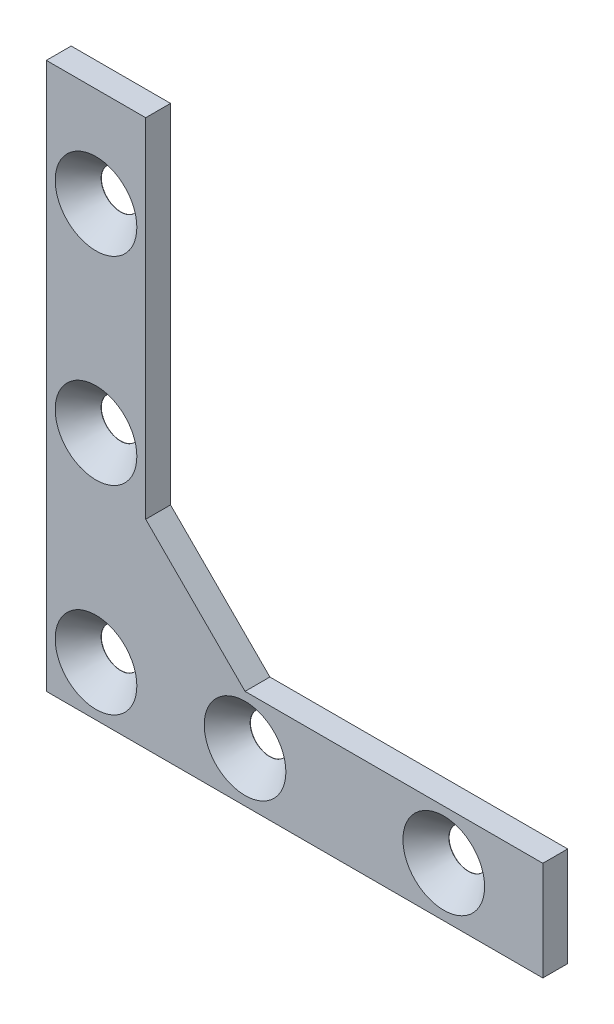
SolidWorks part; units mm, degrees
ref_plane "Front Plane" through (0, 0, 0) normal (0, 0, 1) x (1, 0, 0)
ref_plane "Top Plane" through (0, 0, 0) normal (0, 1, 0) x (1, 0, 0)
ref_plane "Right Plane" through (0, 0, 0) normal (1, 0, 0) x (0, 0, -1)
sketch "Sketch1" plane through (0, 0, 0) normal (0, 0, 1) x (1, 0, 0)
  line L1 (-273.4534, -6.35) -> (-273.4534, 63.5)
  line L2 (-273.4534, 63.5) -> (-260.7534, 63.5)
  line L3 (-273.4534, -6.35) -> (-209.9916, -6.35)
  line L5 (-209.9916, -12.4983) -> (-209.9916, 12.9017) construction
  line L10 (-260.7534, 19.05) -> (-260.7534, 63.5)
  line L11 (-209.9916, -6.35) -> (-209.9916, 6.35)
  line L12 (-209.9916, 6.35) -> (-248.0534, 6.35)
  line L13 (-248.0534, 6.35) -> (-260.7534, 19.05)
  dimension "D1" = 69.85
  dimension "D5" = 12.7
  dimension "D6" = 44.45
extrude "Boss-Extrude1" add sketch "Sketch1" along normal blind 3.175
sketch "Sketch2" plane through (0, 0, 3.175) normal (0, 0, 1) x (1, 0, 0)
  line L0 (-267.1034, 63.5) -> (-267.1034, 50.8) construction
  line L1 (-260.7534, 63.5) -> (-273.4534, 63.5) construction
  line L2 (-267.1034, 50.8) -> (-267.1034, 25.4382) construction
  line L3 (-267.1034, 0.0382) -> (-248.0534, 0.0382) construction
  line L4 (-267.1034, 25.4382) -> (-267.1034, 0.0382) construction
  line L5 (-248.0534, 0.0382) -> (-222.6534, 0.0382) construction
  line L6 (-209.7517, 0) -> (-222.6534, 0.0382) construction
  point P9 (0, 0)
  dimension "D1" = 25.4
  dimension "D2" = 19.05
  dimension "D3" = 25.4
hole_wizard "#10 Clearance Hole1" positions "Sketch3" profile "Sketch4" hole size "#10" standard "ANSI Inch" end condition through all
sketch "Sketch3" plane through (0, 0, 3.175) normal (0, 0, 1) x (1, 0, 0)
  point P0 (-267.1034, 0.0382)
  point P3 (-267.1034, 25.4382)
  point P6 (-267.1034, 50.8)
  point P9 (-248.0534, 0.0382)
  point P12 (-222.6534, 0.0382)
sketch "Sketch4" plane through (-267.1034, 0.0382, 3.175) normal (1, 0, 0) x (0, -1, 0)
  line L0 (0, 0) -> (0, 3.175)
  line L1 (0, 3.175) -> (2.4892, 3.175)
  line L2 (2.4892, 3.175) -> (2.4892, 3.1411)
  line L3 (2.4892, 3.1411) -> (5.2197, 0)
  line L5 (5.2197, 0) -> (0, 0)
  line L6 (-2.4892, 3.1411) -> (-5.2197, 0) construction
  line L11 (0, -6.35) -> (0, 107.95) construction
  dimension "Thru Hole Dia." = 4.9784
  dimension "Thru Hole Depth" = 3.175
  dimension "Near C'Sink Dia." = 10.4394
  dimension "Near C'Sink Angle" = 82
